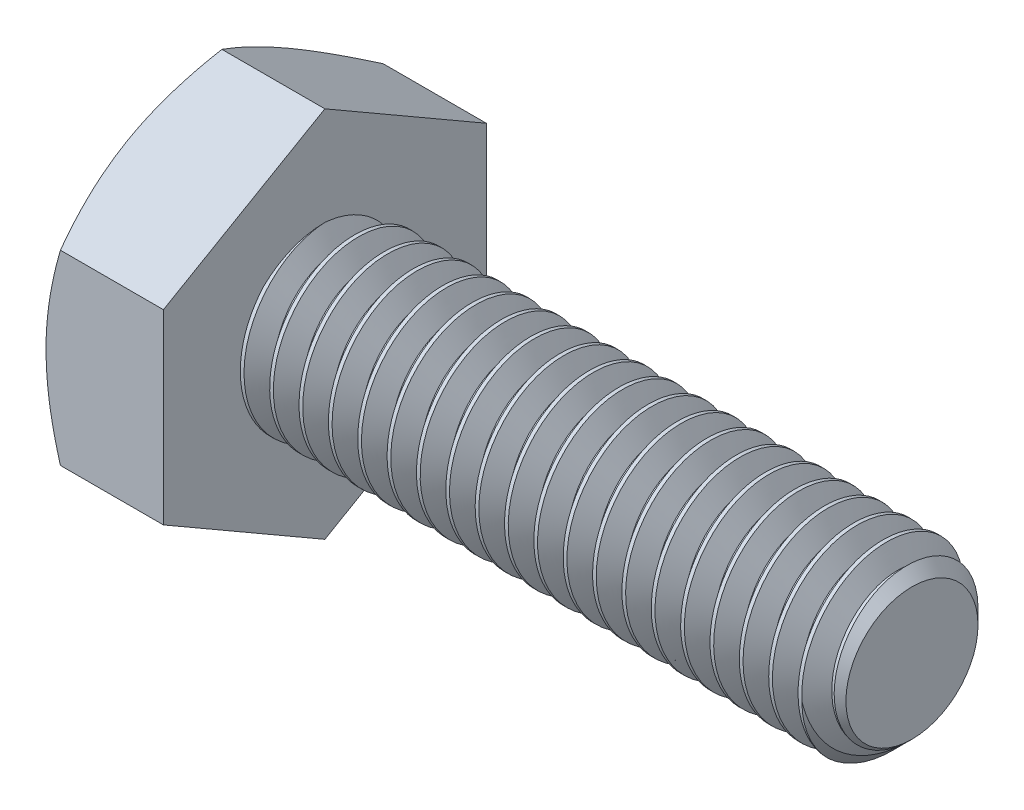
SolidWorks part; units mm, degrees
ref_plane "Front Plane" through (0, 0, 0) normal (0, 0, 1) x (1, 0, 0)
ref_plane "Top Plane" through (0, 0, 0) normal (0, 1, 0) x (1, 0, 0)
ref_plane "Right Plane" through (0, 0, 0) normal (1, 0, 0) x (0, 0, -1)
sketch "Sketch1" plane through (0, 0, 0) normal (0, 0, 1) x (1, 0, 0)
  line L0 (-6, 0) -> (6, 0) construction
  line L1 (-4, 2.75) -> (-4, -2.75) construction
  line L2 (-6, 2.75) -> (-6, -2.75) construction
  line L3 (6, 1.5) -> (6, -1.5) construction
  point P8 (4.25, -1.5)
  dimension "Thread Dia" = 3
  dimension "Hex" = 5.5
  dimension "Head Ht" = 2
  dimension "Length" = 10
  dimension "D1" = 1.75
ref_plane "Plane2" through (6, 0, 0) normal (1, 0, 0) x (0, 0, -1)
sketch "Sketch2" plane through (6, 0, 0) normal (1, 0, 0) x (0, 0, -1)
  circle A0 centre (0, 0) radius 1.5
extrude "Boss-Extrude1" add sketch "Sketch2" against normal up to vertex (10 mm away) up to point (-4, -2.75, 0)
sketch "Sketch4" plane through (6, 0, 0) normal (1, 0, 0) x (0, 0, -1)
  circle A1 centre (0, 0) radius 1.5
  circle A2 centre (0, 0) radius 1.5
  dimension "D1" = 0
curve "Helix/Spiral1" pitch 0.5 height 10.5 turns 21 parameters "Pitch"=0.5
chamfer "Chamfer1" distance 0.375 angle 45 1 edges at (6, 0, -1.5)
sketch "Sketch5" plane through (0, 0, 0) normal (0, 0, 1) x (1, 0, 0)
  line L0 (6, 1.5) -> (6.1875, 1.1752)
  line L1 (6.1875, 1.1752) -> (6.25, 1.1752)
  line L2 (6.25, 1.1752) -> (6.4375, 1.5)
  line L3 (6, 1.5) -> (6.4375, 1.5)
  line L4 (6.2188, 1.1752) -> (6.2188, 1.5) construction
  line L5 (6.0938, 1.3376) -> (6.3438, 1.3376) construction
  line L6 (6, -1.5) -> (6, 1.5) construction
  dimension "D1" = 60
  dimension "D2" = 0.0625
  dimension "D3" = 0.25
sweep "Cut-Sweep1" cut profiles "Sketch5" path "Helix/Spiral1" align with end faces yes
sketch "Sketch3" plane through (-4, 0, 0) normal (-1, 0, 0) x (0, 0, 1)
  line L0 (0, 2.75) -> (0, -2.75) construction
  line L1 (-2.75, -1.5877) -> (0, -3.1754)
  line L2 (0, -3.1754) -> (2.75, -1.5877)
  line L3 (2.75, -1.5877) -> (2.75, 1.5877)
  line L4 (2.75, 1.5877) -> (0, 3.1754)
  line L5 (0, 3.1754) -> (-2.75, 1.5877)
  line L6 (-2.75, 1.5877) -> (-2.75, -1.5877)
  circle A0 centre (0, 0) radius 2.75 construction
extrude "Boss-Extrude2" add sketch "Sketch3" along normal up to vertex (2 mm away) up to point (-6, -2.75, 0)
sketch "Sketch6" plane through (-6, 0, 0) normal (-1, 0, 0) x (0, 0, 1)
  circle A0 centre (0, 0) radius 2.75 construction
  circle A1 centre (0, 0) radius 2.75
extrude "Cut-Extrude1" cut sketch "Sketch6" against normal through all draft 60 flip side to cut
sketch "Sketch9" plane through (0, 0, 0) normal (0, 0, 1) x (1, 0, 0)
  line L0 (-4, 1.5) -> (-4, 0)
  line L1 (-4, 0) -> (-46.5, 0)
  line L2 (-46.5, 0) -> (-48, 1.5)
  line L3 (-48, 1.5) -> (-4, 1.5)
  line L4 (-6, 0) -> (6, 0) construction
  line L5 (-4, 2.75) -> (-4, -2.75) construction
  line L6 (6, 1.5) -> (6, -1.5) construction
  dimension "D1" = 45
  dimension "MinThreadLg" = 54
revolve "Revolve1" [suppressed] add sketch "Sketch9" angle 360 about L1
equation "\"D2@Sketch5\" = \"Pitch@Helix/Spiral1\"*.125"
equation "\"D3@Sketch5\" = \"Pitch@Helix/Spiral1\"*.50"
equation "\"D3@Helix/Spiral1\" = \"Length@Sketch1\"+\"Pitch@Helix/Spiral1\""
equation "\"D1@Chamfer1\" = \"Pitch@Helix/Spiral1\"*.750"
equation "\"D1@Sketch1\" = \"Pitch@Helix/Spiral1\"*3.50"
